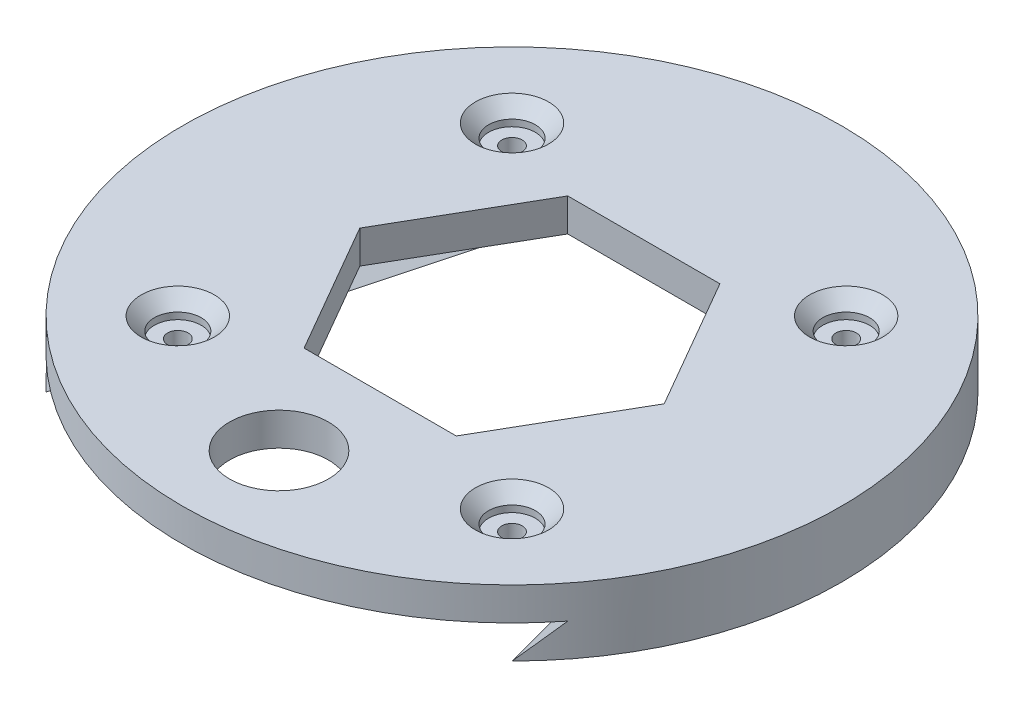
SolidWorks part; units mm, degrees
ref_plane "Front Plane" through (0, 0, 0) normal (0, 0, 1) x (1, 0, 0)
ref_plane "Top Plane" through (0, 0, 0) normal (0, 1, 0) x (1, 0, 0)
ref_plane "Right Plane" through (0, 0, 0) normal (1, 0, 0) x (0, 0, -1)
sketch "Sketch1" plane through (0, 0, 0) normal (0, 1, 0) x (1, 0, 0)
  line L0 (-35.3553, -35.3553) -> (-12.941, 48.2963)
  line L1 (-35.3553, -35.3553) -> (35.3553, -35.3553) construction
  line L2 (-35.3553, -35.3553) -> (-35.3553, 35.3553) construction
  line L3 (-35.3553, 35.3553) -> (35.3553, 35.3553) construction
  line L4 (35.3553, -35.3553) -> (35.3553, 35.3553) construction
  line L5 (-35.3553, -35.3553) -> (35.3553, 35.3553) construction
  line L6 (-35.3553, 35.3553) -> (35.3553, -35.3553) construction
  line L7 (0, 96.5926) -> (0, -94.4212) construction
  line L8 (35.3553, -35.3553) -> (12.941, 48.2963)
  circle A0 centre (0, 0) radius 50
  circle A1 centre (0, -35.3553) radius 7.5
  dimension "D1" = 100
  dimension "D3" = 15
  dimension "D2" = 15
extrude "Boss-Extrude1" add sketch "Sketch1" along normal blind 5 contours A0
extrude "Boss-Extrude2" add sketch "Sketch1<5>" against normal blind 5 contours L8 A0 | L0 A0 region at (-34.0499, 0, -9.1236) region at (34.0499, 0, -9.1236)
sketch "Sketch1<5>" plane through (0, 0, 0) normal (0, 1, 0) x (1, 0, 0) same geometry as "Sketch1"
draft "Draft1" type of draft neutral plane draft angle 45 faces to draft 2 face at (24.1481, -2.5, -6.4705) face at (-24.1481, -2.5, -6.4705) neutral plane through (0, -5, 0) neutral plane normal (0, -1, 0) reverse direction yes parameters "D1"=45
extrude "Cut-Extrude2" cut sketch "Sketch1<8>" against normal through all both and the other way through all contours A1 region at (0, 0, 35.3553)
sketch "Sketch1<8>" plane through (0, 0, 0) normal (0, 1, 0) x (1, 0, 0) same geometry as "Sketch1"
sketch "Sketch2" plane through (0, 0, 0) normal (0, -1, 0) x (1, 0, 0)
  line L1 (23.094, 0) -> (11.547, 20)
  line L2 (11.547, 20) -> (-11.547, 20)
  line L3 (-11.547, 20) -> (-23.094, 0)
  line L4 (-23.094, 0) -> (-11.547, -20)
  line L5 (-11.547, -20) -> (11.547, -20)
  line L6 (11.547, -20) -> (23.094, 0)
  circle A0 centre (0, 0) radius 20 construction
extrude "Cut-Extrude3" cut sketch "Sketch2" against normal through all
sketch "Sketch3" plane through (0, 5, 0) normal (0, 1, 0) x (1, 0, 0)
  line L0 (-25.3553, 25.3553) -> (25.3553, 25.3553) construction
  line L1 (-35.3553, 35.3553) -> (35.3553, 35.3553) construction
  line L2 (-35.3553, 35.3553) -> (-35.3553, -35.3553) construction
  line L3 (-35.3553, -35.3553) -> (35.3553, -35.3553) construction
  line L4 (35.3553, 35.3553) -> (35.3553, -35.3553) construction
  line L5 (-35.3553, 35.3553) -> (35.3553, -35.3553) construction
  line L6 (-35.3553, -35.3553) -> (35.3553, 35.3553) construction
  line L7 (25.3553, 25.3553) -> (25.3553, -25.3553) construction
  line L8 (-25.3553, -25.3553) -> (25.3553, -25.3553) construction
  line L9 (-25.3553, 25.3553) -> (-25.3553, -25.3553) construction
  circle A0 centre (0, 0) radius 50 construction
  circle A1 centre (-25.3553, 25.3553) radius 1.55
  circle A2 centre (-25.3553, 25.3553) radius 3.55
  circle A3 centre (25.3553, 25.3553) radius 1.55
  circle A4 centre (25.3553, 25.3553) radius 3.55
  circle A5 centre (25.3553, -25.3553) radius 1.55
  circle A6 centre (25.3553, -25.3553) radius 3.55
  circle A7 centre (-25.3553, -25.3553) radius 1.55
  circle A8 centre (-25.3553, -25.3553) radius 3.55
  point P0 (0, 0)
  point P30 (0, 0)
  dimension "D1" = 3.1
  dimension "D2" = 10
  dimension "D3" = 2
  dimension "D4" = 4
extrude "Cut-Extrude4" cut sketch "Sketch3" against normal blind 3
extrude "Cut-Extrude6" cut sketch "Sketch3<3>" against normal through all contours A7 | A1 | A3 | A5 region at (-25.3553, 5, 25.3553)
sketch "Sketch3<3>" plane through (0, 5, 0) normal (0, 1, 0) x (1, 0, 0) same geometry as "Sketch3"
chamfer "Chamfer1" distance 2 angle 45 4 edges at (25.3553, 5, -21.8053) (-25.3553, 5, -21.8053) (-25.3553, 5, 28.9053) (25.3553, 5, 28.9053)
